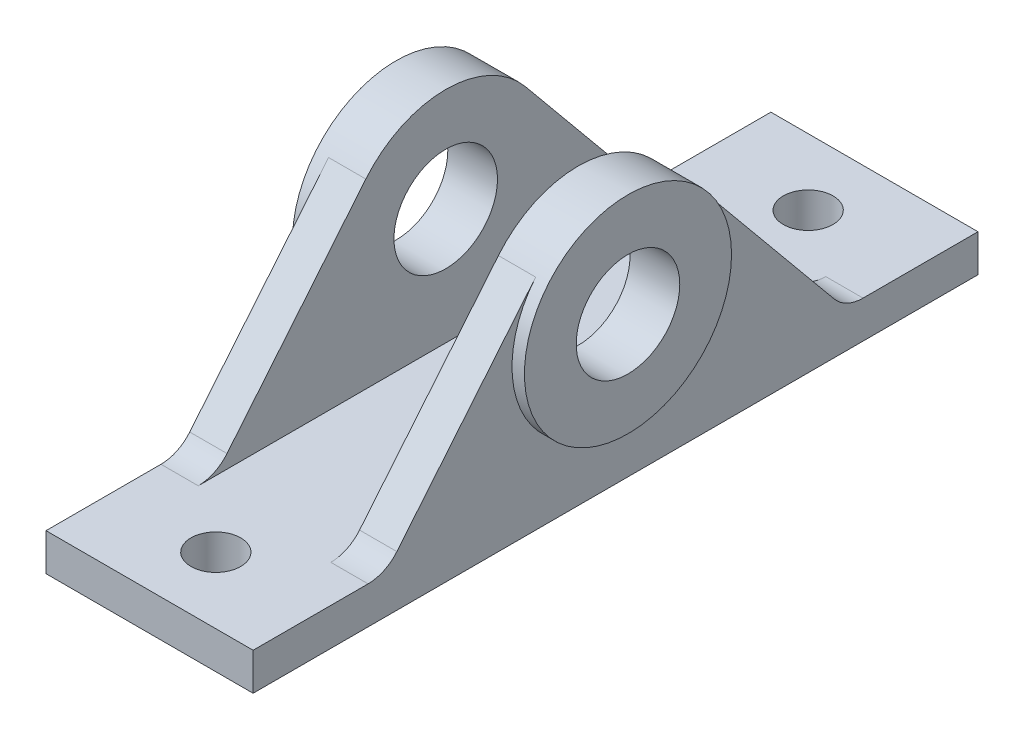
SolidWorks part; units mm, degrees
ref_plane "Front Plane" through (0, 0, 0) normal (0, 0, 1) x (1, 0, 0)
ref_plane "Top Plane" through (0, 0, 0) normal (0, 1, 0) x (1, 0, 0)
ref_plane "Right Plane" through (0, 0, 0) normal (1, 0, 0) x (0, 0, -1)
sketch "Sketch1" plane through (0, 0, 0) normal (0, 1, 0) x (1, 0, 0)
  line L1 (-25, -87.5) -> (25, -87.5)
  line L2 (-25, -87.5) -> (-25, 87.5)
  line L3 (-25, 87.5) -> (25, 87.5)
  line L4 (25, -87.5) -> (25, 87.5)
  line L5 (-25, -87.5) -> (25, 87.5) construction
  line L6 (-25, 87.5) -> (25, -87.5) construction
  point P0 (0, 0)
  dimension "D1" = 175
  dimension "D2" = 50
extrude "Boss-Extrude1" add sketch "Sketch1" along normal blind 9
sketch "Sketch2" plane through (0, 9, 0) normal (0, 1, 0) x (1, 0, 0)
  line L0 (25, -87.5) -> (25, 87.5) construction
  line L1 (-25, -87.5) -> (25, -87.5) construction
  circle A0 centre (0, -71.5) radius 6
  dimension "D3" = 12
  dimension "D1" = 25
  dimension "D2" = 16
extrude "Cut-Extrude1" cut sketch "Sketch2" against normal through all
mirror "Mirror1" about plane through (0, 0, 0) normal (0, 0, 1) of "Cut-Extrude1"
sketch "Sketch3" plane through (25, 0, 0) normal (1, 0, 0) x (0, 0, -1)
  line L0 (-87.5, 9) -> (87.5, 9) construction
  line L1 (-55.5, 9) -> (-19.2864, 52.907)
  line L2 (55.5, 9) -> (19.2864, 52.907)
  line L3 (-55.5, 9) -> (55.5, 9)
  line L4 (87.5, 9) -> (87.5, 0) construction
  line L5 (0, 0) -> (0, 62) construction
  circle A0 centre (0, 37) radius 25
  circle A1 centre (0, 37) radius 12.5
  point P4 (0, 9)
  line M4 (87.5, 9) -> (-87.5, 9)
  dimension "D1" = 50
  dimension "D5" = 25
  dimension "D2" = 28
  dimension "D3" = 32
  dimension "D4" = 32
extrude "Boss-Extrude2" add sketch "Sketch3" against normal blind 9 contours L3 L5 A0 L1 | L5 L2 A0 M4 region at (25, 19.9243, 30.1614) region at (25, 19.9243, -30.1614)
extrude "Boss-Extrude3" add sketch "Sketch3<3>" along normal blind 3 and the other way blind 9 contours A0 L5 A1 | L5 A0 A1 region at (25, 59.1071, 10.4229) region at (25, 59.1071, -10.4229)
sketch "Sketch3<3>" plane through (25, 0, 0) normal (1, 0, 0) x (0, 0, -1) same geometry as "Sketch3"
fillet "Fillet1" radius 9 2 edges at (20.5, 9, -55.5) (20.5, 9, 55.5)
mirror "Mirror4" about plane through (0, 0, 0) normal (1, 0, 0) of "Boss-Extrude3", "Boss-Extrude2", "Fillet1"
